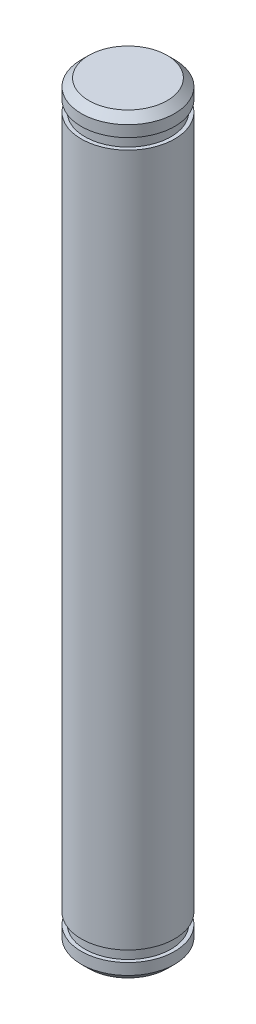
SolidWorks part; units mm, degrees
ref_plane "Front" through (0, 0, 0) normal (0, 0, 1) x (1, 0, 0)
ref_plane "Top" through (0, 0, 0) normal (0, 1, 0) x (1, 0, 0)
ref_plane "Right" through (0, 0, 0) normal (1, 0, 0) x (0, 0, -1)
ref_axis "side-side" through (80.9, 0, 0) along (-1, 0, 0)
ref_axis "up-down" through (0, 50, 0) along (0, -1, 0)
ref_axis "front-back" through (0, 0, -80.9) along (0, 0, 1)
sketch "Sketch1" plane through (0, 0, 0) normal (0, 0, 1) x (1, 0, 0)
  line L0 (-3.175, 23.5585) -> (-3.175, -23.5585)
  line L1 (0, 25.5651) -> (-3.175, 25.5651)
  line L2 (0, 25.5651) -> (0, -25.5651)
  line L3 (0, -25.5651) -> (-3.175, -25.5651)
  line L4 (-3.175, 25.5651) -> (-3.175, 24.2951)
  line L5 (-3.175, 24.2951) -> (-2.921, 24.2951)
  line L6 (-3.175, -24.2951) -> (-3.175, -25.5651)
  line L7 (-3.175, 23.5585) -> (-2.921, 23.5585)
  line L8 (-2.921, 24.2951) -> (-2.921, 23.5585)
  line L9 (-3.175, -23.5585) -> (-2.921, -23.5585)
  line L10 (0, 25.5651) -> (0, 13.3378) construction
  line L11 (-3.175, -24.2951) -> (-2.921, -24.2951)
  line L12 (-2.921, -23.5585) -> (-2.921, -24.2951)
  line L13 (0.9853, 22.7965) -> (-9.9695, 22.7965) construction
  dimension "D1" = 6.35
  dimension "D2" = 0.7366
  dimension "D3" = 1.27
  dimension "D4" = 47.117
  dimension "D5" = 0.254
  dimension "D6" = 0.762
revolve "Revolve1" add sketch "Sketch1" angle 360 about L10
chamfer "Chamfer1" distance 0.508 angle 45 2 edges at (-3.175, -25.5651, 0) (-3.175, 25.5651, 0)
